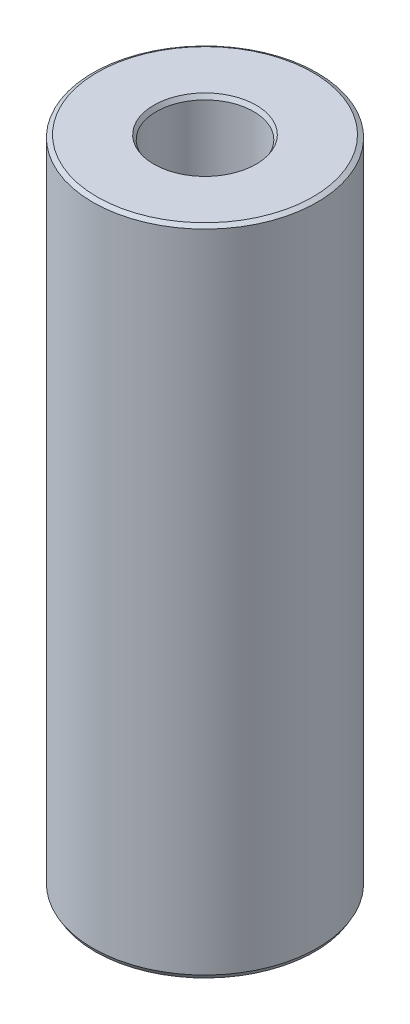
SolidWorks part; units mm, degrees
ref_plane "Front Plane" through (0, 0, 0) normal (0, 0, 1) x (1, 0, 0)
ref_plane "Top Plane" through (0, 0, 0) normal (0, 1, 0) x (1, 0, 0)
ref_plane "Right Plane" through (0, 0, 0) normal (1, 0, 0) x (0, 0, -1)
sketch "Sketch1" plane through (0, 0, 0) normal (0, 1, 0) x (1, 0, 0)
  circle A0 centre (0, 0) radius 50
  dimension "SLEEVE_OD" = 100
extrude "Boss-Extrude1" add sketch "Sketch1" along normal blind 291.017
sketch "Sketch2" plane through (0, 0, 0) normal (0, 1, 0) x (1, 0, 0)
  circle A0 centre (0, 0) radius 21.7057
  dimension "BORE_D" = 43.4114
extrude "Cut-Extrude1" cut sketch "Sketch2" along normal through all
chamfer "Chamfer1" distance 1.1067 angle 60 4 edges at (0, 291.017, 21.7057) (0, 0, 21.7057) (0, 0, 50) (0, 291.017, 50) first distance on face at (0, 291.017, 21.7057) first distance on face at (0, 0, 21.7057) first distance on face at (0, 291.017, 50)
